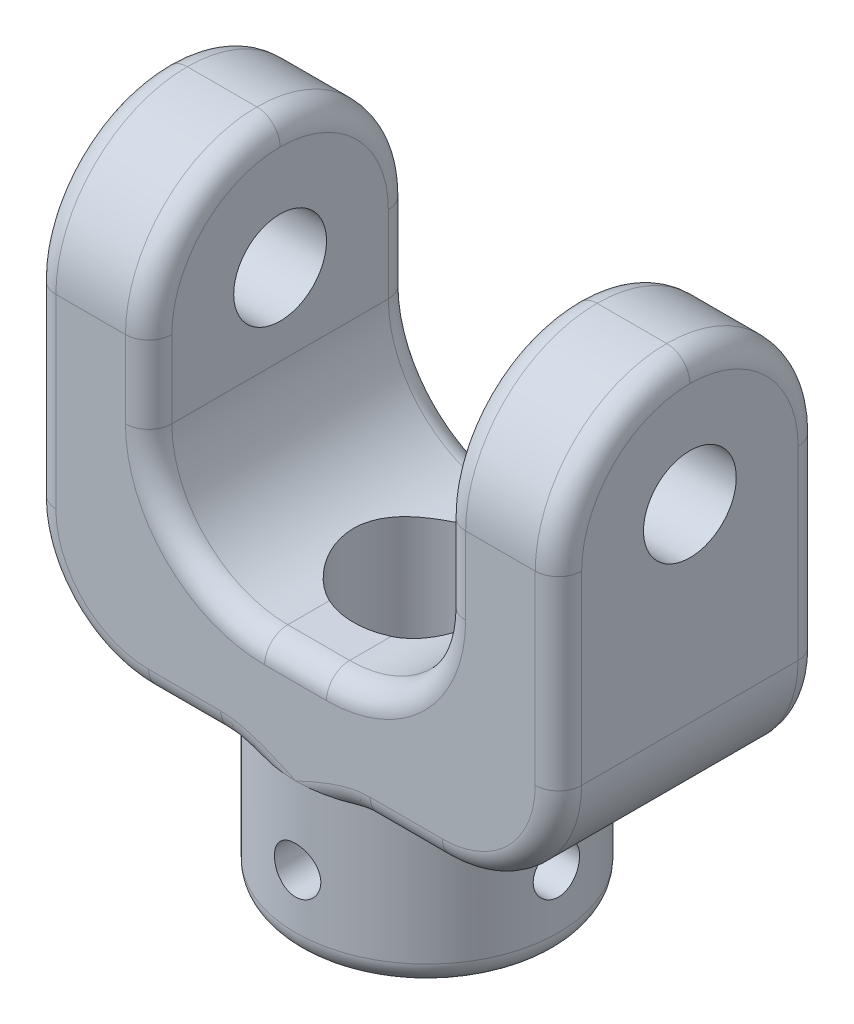
SolidWorks part; units mm, degrees
material "AISI 1045 Çelik, soğuk çekilmiş"
ref_plane "Ön Düzlem" through (0, 0, 0) normal (0, 0, 1) x (1, 0, 0)
ref_plane "Üst Düzlem" through (0, 0, 0) normal (0, 1, 0) x (1, 0, 0)
ref_plane "Sağ Düzlem" through (0, 0, 0) normal (1, 0, 0) x (0, 0, -1)
sketch "Çizim1" plane through (0, 0, 0) normal (0, 0, 1) x (1, 0, 0)
  line L1 (-19, 14) -> (19, 14)
  line L2 (19, 14) -> (19, 56)
  line L3 (19, 56) -> (34, 56)
  line L4 (34, 56) -> (34, 0)
  line L5 (34, 0) -> (-34, 0)
  line L6 (-34, 56) -> (-34, 0)
  line L7 (-19, 56) -> (-34, 56)
  line L8 (-19, 14) -> (-19, 56)
  line L9 (0, 0) -> (0, 14) construction
  dimension "D1" = 14
  dimension "D3" = 15
  dimension "D4" = 56
extrude "Yükseklik-Ekstrüzyon1" add sketch "Çizim1" along normal mid plane 34
fillet "Radyus1" radius 17 4 edges at (26.5, 56, 17) (26.5, 56, -17) (-26.5, 56, -17) (-26.5, 56, 17)
sketch "Çizim2" plane through (0, 0, 0) normal (0, -1, 0) x (1, 0, 0)
  circle A0 centre (0, 0) radius 17
  dimension "D1" = 34
extrude "Yükseklik-Ekstrüzyon2" add sketch "Çizim2" along normal blind 20
fillet "Radyus2" radius 3 1 edges at (0, -20, -17)
fillet "Radyus3" radius 15 2 edges at (-34, 0, 0) (34, 0, 0)
fillet "Radyus4" radius 3 16 edges at (-34, 51.0208, 12.0208) (-34, 51.0208, -12.0208) (-34, 27, -17) (-29.6066, 4.3934, -17) (-9.5, 0, -17) (9.5, 0, -17) (29.6066, 4.3934, -17) (34, 27, -17) (34, 51.0208, -12.0208) (34, 51.0208, 12.0208) (34, 27, 17) (29.6066, 4.3934, 17) (9.5, 0, 17) (-9.5, 0, 17) (-29.6066, 4.3934, 17) (-34, 27, 17)
fillet "Radyus6" radius 15 2 edges at (19, 14, 0) (-19, 14, 0)
fillet "Radyus7" radius 3 14 edges at (-14.6066, 18.3934, 17) (0, 14, 17) (14.6066, 18.3934, 17) (19, 34, 17) (19, 51.0208, 12.0208) (19, 51.0208, -12.0208) (19, 34, -17) (14.6066, 18.3934, -17) (0, 14, -17) (-14.6066, 18.3934, -17) (-19, 34, -17) (-19, 51.0208, -12.0208) (-19, 51.0208, 12.0208) (-19, 34, 17)
sketch "Çizim3" plane through (0, -20, 0) normal (0, -1, 0) x (-1, 0, 0)
  circle A0 centre (0, 0) radius 9.5
  dimension "D1" = 19
extrude "Kes-Ekstrüzyon3" cut sketch "Çizim3" against normal blind 54
sketch "Çizim4" plane through (34, 0, 0) normal (1, 0, 0) x (0, 0, -1)
  circle A0 centre (0, 39.5) radius 6
  point P2 (0, 45.5)
  dimension "D1" = 12
  dimension "D2" = 10.5
extrude "Kes-Ekstrüzyon4" cut sketch "Çizim4" against normal blind 75
sketch "Çizim5" plane through (0, 0, 17) normal (0, 0, 1) x (1, 0, 0)
  line L1 (-14, -20) -> (14, -20) construction
  circle A0 centre (0, -10) radius 3
  dimension "D1" = 6
  dimension "D2" = 10
extrude "Kes-Ekstrüzyon6" cut sketch "Çizim5" against normal blind 13
pattern_circular "Dairesel Kaplama1" count 4 every 90 about axis through (0, -20, 0) along (0, 1, 0) of "Kes-Ekstrüzyon6"
